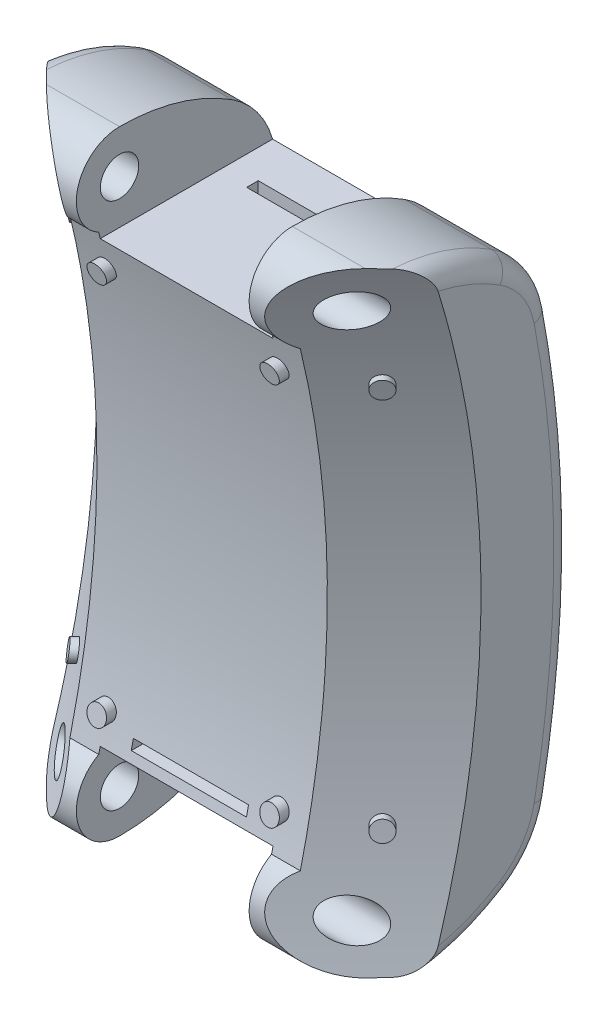
SolidWorks part; units mm, degrees
ref_plane "Alzado" through (0, 0, 0) normal (0, 0, 1) x (1, 0, 0)
ref_plane "Planta" through (0, 0, 0) normal (0, 1, 0) x (1, 0, 0)
ref_plane "Vista lateral" through (0, 0, 0) normal (1, 0, 0) x (0, 0, -1)
sketch "Croquis3" plane through (0, 0, 0) normal (1, 0, 0) x (0, 0, -1)
  circle A2 centre (-0.6486, 27.5) radius 2
  arc A3 (-2.8138, -23.5551) -> (3.6883, -28.7004) centre (-0.6486, -27.5) ccw
  arc A4 (3.6883, 28.7004) -> (-2.8138, 23.5551) centre (-0.6486, 27.5) ccw
  circle A5 centre (-0.6486, -27.5) radius 2
  arc A6 (-2.8138, -23.5551) -> (-2.8138, 23.5551) centre (-100, 0) ccw
  arc A7 (3.6883, -28.7004) -> (3.6883, 28.7004) centre (-100, 0) ccw
  point P0 (0, 0)
  point P1 (7.5871, 0)
  dimension "D2" = 4
  dimension "D3" = 9
  dimension "D1" = 100
  dimension "D5" = 55
extrude "Base pieza" add sketch "Croquis3" along normal blind 20
sketch "Croquis4" plane through (0, 0, 0) normal (0, 1, 0) x (1, 0, 0)
  line L2 (20, 8.0687) -> (4.9289, -7.0024)
  line L3 (20, 3.6883) -> (20, 7.5871) construction
sketch "Croquis5" plane through (20, 0, 0) normal (1, 0, 0) x (0, 0, -1)
  line L1 (14.3209, 0) -> (-14.3209, 0) construction
  line L3 (-7.8933, 38.9405) -> (0.3071, 38.463)
  line L4 (-7.8933, -38.9405) -> (0.3071, -38.463)
  arc A1 (0.3071, -38.463) -> (0.3071, 38.463) centre (-92, 0) ccw
  arc A2 (-7.8933, -38.9405) -> (-4.5341, -29.7701) centre (-100, 0) ccw
  arc A3 (-2.8138, -23.5551) -> (-2.8138, 23.5551) centre (-100, 0) ccw construction
  arc A9 (3.6883, 28.7004) -> (-2.8138, 23.5551) centre (-0.6486, 27.5) ccw construction
  arc A11 (-2.8138, -23.5551) -> (3.6883, -28.7004) centre (-0.6486, -27.5) ccw construction
  arc A12 (-2.8138, -23.5551) -> (-4.5341, -29.7701) centre (-0.6486, -27.5) ccw
  arc A13 (-2.8138, -23.5551) -> (-2.8138, 23.5551) centre (-100, 0) ccw
  arc A14 (-4.5341, 29.7701) -> (-2.8138, 23.5551) centre (-0.6486, 27.5) ccw
  arc A15 (-4.5341, 29.7701) -> (-7.8933, 38.9405) centre (-100, 0) ccw
  dimension "D1" = 100
  dimension "D3" = 8
  dimension "D2" = 11
  dimension "D4" = 11
sketch "Croquis8" plane through (0, 0, 0) normal (1, 0, 0) x (0, 0, -1)
  line L1 (14.3209, 0) -> (-14.3209, 0) construction
  line L2 (-0.6486, -27.5) -> (3.6883, -28.7004) construction
  arc A0 (3.6883, 28.7004) -> (-2.8138, 23.5551) centre (-0.6486, 27.5) ccw construction
  arc A1 (15.5065, -22.0218) -> (15.5065, 22.0218) centre (-100, 0) ccw
  arc A2 (11.0696, 28.5745) -> (-0.6486, 32) centre (-0.6486, 10.2437) ccw
  arc A3 (3.6883, 28.7004) -> (-0.6486, 32) centre (-0.6486, 27.5) ccw
  arc A4 (15.5065, 22.0218) -> (11.0696, 28.5745) centre (5.6835, 20.149) ccw
  arc A5 (-2.8138, -23.5551) -> (-2.8138, 23.5551) centre (-100, 0) ccw
  arc A6 (3.6883, 28.7004) -> (-2.8138, 23.5551) centre (-0.6486, 27.5) ccw
  arc A7 (3.6883, -28.7004) -> (3.6883, 28.7004) centre (-100, 0) ccw
  arc A8 (-2.8138, -23.5551) -> (3.6883, -28.7004) centre (-0.6486, -27.5) ccw
  arc A9 (15.5065, -22.0218) -> (11.0696, -28.5745) centre (5.6835, -20.149) cw
  arc A10 (3.6883, -28.7004) -> (-0.6486, -32) centre (-0.6486, -27.5) cw
  arc A11 (3.6883, -28.7004) -> (3.6883, 28.7004) centre (-100, 0) ccw
  arc A12 (11.0696, -28.5745) -> (-0.6486, -32) centre (-0.6486, -10.2437) cw
  arc A13 (3.6883, -28.7004) -> (3.6883, 28.7004) centre (-100, 0) ccw construction
  arc A14 (-2.8138, -23.5551) -> (3.6883, -28.7004) centre (-0.6486, -27.5) ccw construction
  dimension "D4" = 10
  dimension "D2" = 10
extrude "Chepa" add sketch "Croquis8" along normal blind 20
sweep "Chaflán" cut profiles "Croquis5" path "Croquis4"
sketch "Croquis6" plane through (0, 0, 0) normal (-1, 0, 0) x (0, 0, 1)
  line L1 (-17.7404, 39.8126) -> (14.3074, 39.8126)
  line L2 (-17.7404, 39.8126) -> (-17.7404, 22.9)
  line L3 (-17.7404, 22.9) -> (14.3074, 22.9)
  line L4 (14.3074, 39.8126) -> (14.3074, 22.9)
  line L10 (14.3209, 0) -> (-14.3209, 0) construction
  line L11 (14.3074, -39.8126) -> (14.3074, -22.9)
  line L12 (-17.7404, -22.9) -> (14.3074, -22.9)
  line L13 (-17.7404, -39.8126) -> (-17.7404, -22.9)
  line L14 (-17.7404, -39.8126) -> (14.3074, -39.8126)
  circle A1 centre (0.6486, 27.5) radius 2 construction
  dimension "D1" = 4.6
extrude "Corte superior/inferior" cut sketch "Croquis6" against normal blind 9
sketch "Croquis18" plane through (0, 0, 0) normal (-1, 0, 0) x (0, 0, 1)
  line L6 (-10.7976, 22.9) -> (-10.7976, 18.1099)
  line L7 (-15.2976, 22.9) -> (2.6574, 22.9) construction
  line L8 (-10.7976, 18.1099) -> (-9.5976, 18.1099)
  line L9 (-9.5976, 18.1099) -> (-9.5976, 22.9)
  line L10 (-9.5976, 22.9) -> (-10.7976, 22.9)
  dimension "D1" = 4.5
  dimension "D2" = 1.2
extrude "Ranura inferior" cut sketch "Croquis18" against normal blind 6
ref_plane "Plano1" through (8.5819, 0, 8.5819) normal (0.7071, 0, 0.7071) x (0, 1, 0)
sketch "Croquis11" plane through (8.5819, 0, 8.5819) normal (0.7071, 0, 0.7071) x (0, 1, 0)
  line L0 (0, -19.799) -> (0, -8.4853) construction
  line L1 (0, -14.3209) -> (0, 14.3209) construction
  line L2 (-23.5551, -6.4956) -> (-23.5551, -17.8093) construction
  line L3 (-22.9, 1.879) -> (-22.9, -4.4849) construction
  circle A0 centre (19.9, -12.5424) radius 1
  circle A1 centre (-19.9, -12.5424) radius 1
  spline S0 degree 3 poles (-31.7191, -16.1476) (-10.95, -21.0595) (10.95, -21.0595) (31.7191, -16.1476) knots 0.09302 0.09302 0.09302 0.09302 0.90698 0.90698 0.90698 0.90698 weights 0.987019 0.953041 0.953041 0.987019 construction
  spline S1 degree 3 poles (23.5551, -6.4956) (8.0018, -9.1612) (-8.0018, -9.1612) (-23.5551, -6.4956) knots 0.201372 0.201372 0.201372 0.201372 0.798628 0.798628 0.798628 0.798628 weights 0.975256 0.956962 0.956962 0.975256 construction
  dimension "D1" = 3
  dimension "D2" = 2
extrude "Salientes chaflán" add sketch "Croquis11" against normal up to surface (2.2371 mm away) up to face at (17.1454, -27.3145, -1.3427)
sketch "Croquis10" plane through (0, 0, 0) normal (0, 0, 1) x (1, 0, 0)
  line L0 (9, 22.9) -> (0, 22.9) construction
  line L2 (12, 23.5551) -> (12, -23.5551) construction
  line L3 (14.3209, 0) -> (-14.3209, 0) construction
  circle A0 centre (9, 19.9) radius 1
  circle A1 centre (9, -19.9) radius 1
  dimension "D1" = 2
  dimension "D3" = 3
  dimension "D2" = 3
extrude "Salientes" add sketch "Croquis10" along normal blind 3.43
sketch "Croquis14" plane through (20, 0, 0) normal (1, 0, 0) x (0, 0, -1)
  line L0 (14.3209, 0) -> (-14.3209, 0) construction
  line L1 (-2.8328, -43.2422) -> (-15.7368, -43.2422)
  line L2 (-15.7368, -43.2422) -> (-15.7368, 39.4979)
  line L3 (-15.7368, 39.4979) -> (-1.131, 39.4979)
  arc A1 (2.8362, -31.7191) -> (2.8362, 31.7191) centre (-92, 0) ccw construction
  arc A2 (-2.8328, -43.2422) -> (-1.131, 39.4979) centre (-93, 0) ccw
  dimension "D1" = 100
  dimension "D2" = 1
sweep "Alisar salientes laterales" cut profiles "Croquis14" path "Croquis4<3>"
sketch "Croquis4<3>" plane through (0, 0, 0) normal (0, 1, 0) x (1, 0, 0) same geometry as "Croquis4"
sketch "Croquis16" plane through (0, 0, 0) normal (1, 0, 0) x (0, 0, -1)
  line L1 (-3.6523, -22.7623) -> (-3.748, 23.1634)
  arc A0 (-3.6523, -22.7623) -> (-3.748, 23.1634) centre (-100, 0) ccw
  arc A1 (-2.8138, -23.5551) -> (-2.8138, 23.5551) centre (-100, 0) ccw construction
  dimension "D1" = 1
extrude "Alisar salientes" cut sketch "Croquis16" against normal through all and the other way through all contours L1 A0
sketch "Croquis9" plane through (0, 0, 0) normal (0, 0, 1) x (1, 0, 0)
  line L0 (0, -22.9) -> (9, -22.9) construction
  line L1 (0, -20.9) -> (6, -20.9)
  line L3 (0, -21.9) -> (6, -21.9)
  line L4 (6, -20.9) -> (6, -21.9)
  line L5 (12, 23.5551) -> (12, -23.5551) construction
  line L6 (0, -20.9) -> (0, -21.9)
  dimension "D1" = 1
  dimension "D3" = 6
extrude "Ranura superior" cut sketch "Croquis9" against normal blind 0.1 and the other way through all
sketch "Croquis21" plane through (0, 0, 0) normal (1, 0, 0) x (0, 0, -1)
  line L1 (0, 11) -> (0, -11) construction
  line L3 (0, -23.3488) -> (0, -12.0984) construction
  line L4 (0, -13.3488) -> (8.157, -13.3488) construction
  arc A2 (-0.4859, -23.337) -> (10, -13.3488) centre (0, -13.3488) ccw
  dimension "D1" = 20
sweep "Ranura superior v2" cut profiles "Croquis9<2>" path "Croquis21"
sketch "Croquis9<2>" plane through (0, 0, 0) normal (0, 0, 1) x (1, 0, 0) same geometry as "Croquis9"
sketch "Croquis17" plane through (0, 0, 0) normal (-1, 0, 0) x (0, 0, 1)
  line L0 (0.3673, -20.9) -> (2.2084, -20.9) construction
  line L1 (-17.5871, 19.9) -> (-5.5871, 19.9)
  line L2 (-17.5871, 19.9) -> (-17.5871, -17.9)
  line L3 (-17.5871, -17.9) -> (-5.5871, -17.9)
  line L4 (-5.5871, 19.9) -> (-5.5871, -17.9)
  line L5 (-15.2976, 22.9) -> (-10.7976, 22.9) construction
  arc A0 (-15.5065, 22.0218) -> (-15.5065, -22.0218) centre (100, 0) ccw construction
  dimension "D1" = 3
  dimension "D2" = 3
  dimension "D3" = 12
extrude "Aligerar" cut sketch "Croquis17" against normal blind 14.5
sketch "Croquis22" plane through (0, -17.9, 0) normal (0, 1, 0) x (1, 0, 0)
  line L0 (6, 10.7976) -> (0, 10.7976) construction
  line L1 (0, 9.2394) -> (6, 9.2394)
  line L2 (0, 9.2394) -> (0, 8.2394)
  line L3 (0, 8.2394) -> (6, 8.2394)
  line L4 (6, 9.2394) -> (6, 8.2394)
  line L5 (0, 9.2394) -> (6, 8.2394) construction
  line L6 (0, 8.2394) -> (6, 9.2394) construction
  line L9 (0, 15.2976) -> (0, 10.7976) construction
  line L10 (6, 7.2394) -> (0, 7.2394) construction
  point P0 (3, 8.7394)
  dimension "D1" = 1
  dimension "D2" = 1
extrude "Cortar-Extruir1" cut sketch "Croquis22" against normal blind 10
mirror "Simetría1" about plane through (0, 0, 0) normal (1, 0, 0) of "Cortar-Extruir1", "Ranura inferior", "Salientes chaflán", "Salientes", "Alisar salientes laterales", "Ranura superior", "Base pieza", "Chaflán", "Corte superior/inferior", "Chepa", "Aligerar", "Alisar salientes", "Ranura superior v2"
fillet "Redondeo posterior" radius 2 10 edges at (20, -30.5681, -7.1138) (20, -25.7557, -13.9638) (20, 30.5681, -7.1138) (20, 25.7557, -13.9638) (-20, -30.5681, -7.1138) (-20, -25.7557, -13.9638) (-20, 30.5681, -7.1138) (-20, 25.7557, -13.9638) (20, 0, -17.5871) (-20, 0, -17.5871)
fillet "Redondeo1" radius 1 4 edges at (14.5, 1, -5.5871) (0, 19.9, -5.5871) (-14.5, 1, -5.5871) (0, -17.9, -5.5871)
equation "\"Wp\"= 9'Ancho de dedo"
equation "\"Hp\"= 46'Altura superficie útil"
equation "\"RdC\"= 100'Radio de curvatura"
equation "\"Drill\"= 4'Diámetro taladro"
equation "\"Lp\"= 40'Largo pieza"
equation "\"Chamfer\" =8'Chaflán"
equation "\"D2@Croquis3\"=\"Drill\""
equation "\"D3@Croquis3\"=\"Wp\""
equation "\"D1@Croquis3\"=\"RdC\""
equation "\"D5@Croquis3\"=\"Hp\"+\"Wp\""
equation "\"D1@Base pieza\" = \"Lp\" / 2"
equation "\"D1@Croquis5\"=\"RdC\""
equation "\"D3@Croquis5\"=\"Chamfer\""
equation "\"D1@Corte superior/inferior\" = \"Lp\" / 2 - \"Chamfer\" - 3"
equation "\"D2@Croquis8\"=10"
equation "\"D2@Croquis5\"=\"Wp\"+2"
equation "\"D4@Croquis5\"=\"Wp\"+2"
equation "\"D1@Croquis6\"=\"Wp\"/2+0.1"
equation "\"D1@Ranura inferior\"=\"Wp\"-3"
